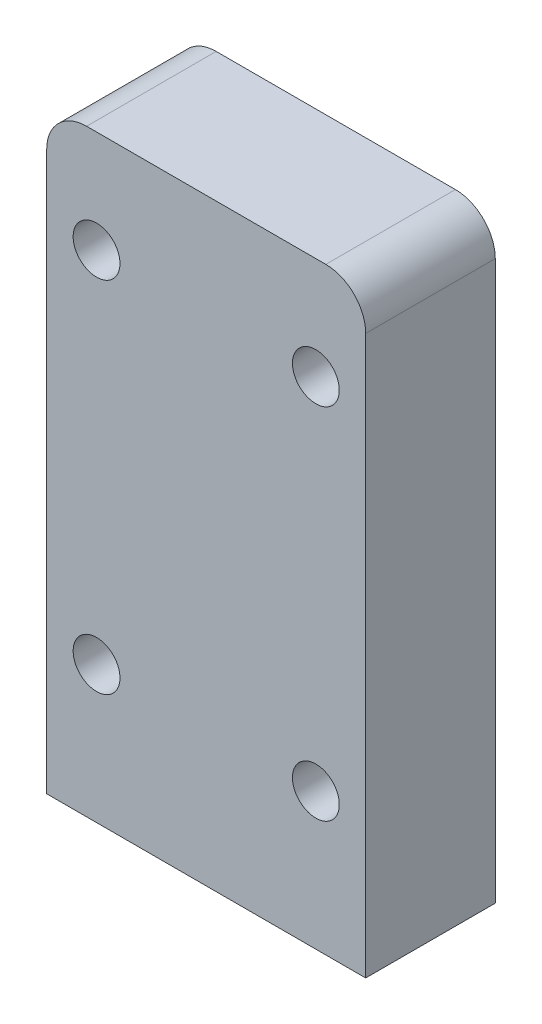
SolidWorks part; units mm, degrees
ref_plane "Front Plane" through (0, 0, 0) normal (0, 0, 1) x (1, 0, 0)
ref_plane "Top Plane" through (0, 0, 0) normal (0, 1, 0) x (1, 0, 0)
ref_plane "Right Plane" through (0, 0, 0) normal (1, 0, 0) x (0, 0, -1)
sketch "Sketch1" plane through (0, 0, 0) normal (0, 0, 1) x (1, 0, 0)
  line L1 (0, 0) -> (16, 0)
  line L2 (0, 0) -> (0, 30)
  line L3 (0, 30) -> (16, 30)
  line L4 (16, 0) -> (16, 30)
  dimension "D1" = 30
  dimension "D2" = 16
extrude "Boss-Extrude1" add sketch "Sketch1" along normal blind 6.5
sketch "Sketch3" plane through (0, 0, 0) normal (0, 0, -1) x (-1, 0, 0)
  line L0 (-13.5, 6.87) -> (-2.5, 6.87) construction
  line L1 (0, 0) -> (-16, 0) construction
  circle A0 centre (-13.5, 6.87) radius 1.175
  circle A1 centre (-2.5, 6.87) radius 1.175
  circle A2 centre (-2.5, 24.87) radius 1.175
  circle A3 centre (-13.5, 24.87) radius 1.175
  point P8 (-8, 6.87)
  point P11 (-8, 0)
  dimension "D1" = 2.35
  dimension "D2" = 11
  dimension "D3" = 18
  dimension "D4" = 6.87
extrude "Cut-Extrude1" cut sketch "Sketch3" against normal through all
fillet "Fillet1" radius 2 2 edges at (16, 30, 3.25) (0, 30, 3.25)
sketch "Sketch4" plane through (0, 0, 0) normal (0, -1, 0) x (1, 0, 0)
  line L0 (13.5, 3.25) -> (2.5, 3.25) construction
  line L3 (0, 0) -> (16, 0) construction
  line L6 (16, 6.5) -> (16, 0) construction
  circle A0 centre (13.5, 3.25) radius 1.13
  circle A1 centre (2.5, 3.25) radius 1.13
  point P4 (8, 3.25)
  point P7 (8, 0)
  point P10 (16, 3.25)
  dimension "D1" = 2.26
  dimension "D2" = 11
ref_plane "center plane" through (8, 0, 0) normal (1, 0, 0) x (0, 0, -1)
extrude "Cut-Extrude2" cut sketch "Sketch4" against normal blind 4
